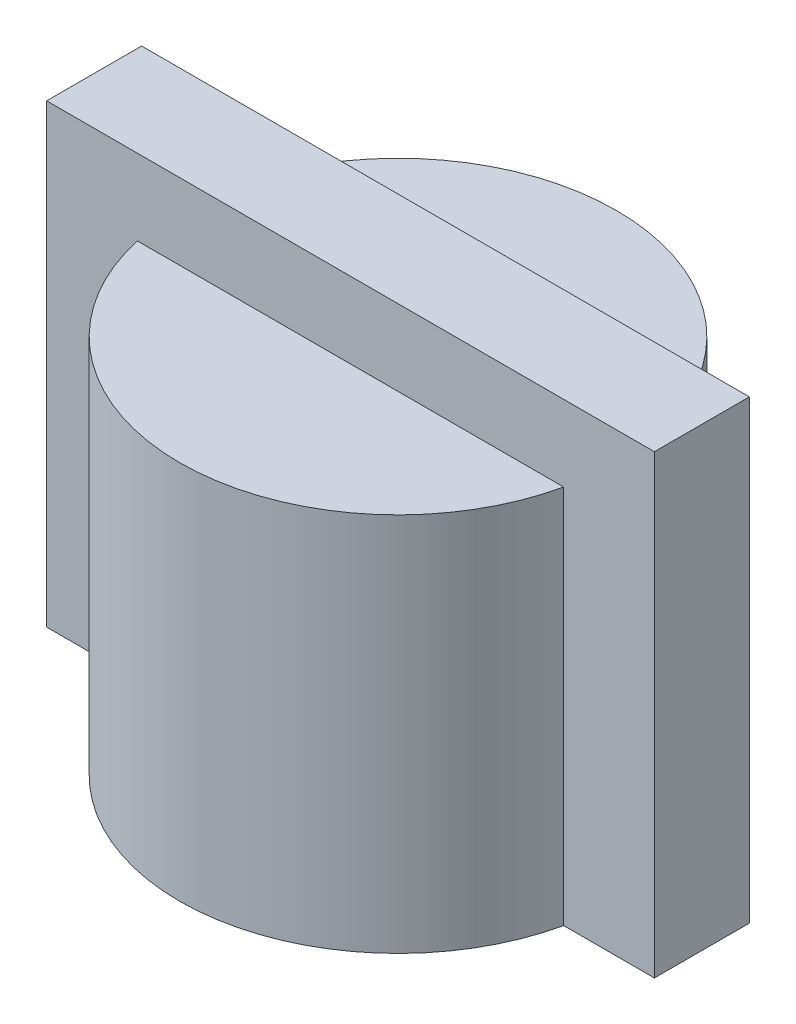
SolidWorks part; units mm, degrees
ref_plane "Front Plane" through (0, 0, 0) normal (0, 0, 1) x (1, 0, 0)
ref_plane "Top Plane" through (0, 0, 0) normal (0, 1, 0) x (1, 0, 0)
ref_plane "Right Plane" through (0, 0, 0) normal (1, 0, 0) x (0, 0, -1)
sketch "Sketch1" plane through (0, 0, 0) normal (0, 1, 0) x (1, 0, 0)
  circle A0 centre (0, 0) radius 5.75
  dimension "D1" = 11.5
extrude "Boss-Extrude1" add sketch "Sketch1" along normal blind 10
sketch "Sketch2" plane through (0, 0, 0) normal (0, -1, 0) x (-1, 0, 0)
  line L1 (8, -1.25) -> (-8, -1.25)
  line L2 (8, -1.25) -> (8, 1.25)
  line L3 (8, 1.25) -> (-8, 1.25)
  line L4 (-8, -1.25) -> (-8, 1.25)
  line L5 (8, -1.25) -> (-8, 1.25) construction
  line L6 (8, 1.25) -> (-8, -1.25) construction
  point P0 (0, 0)
  dimension "D1" = 16
  dimension "D2" = 2.5
extrude "Boss-Extrude2" add sketch "Sketch2" against normal blind 12
